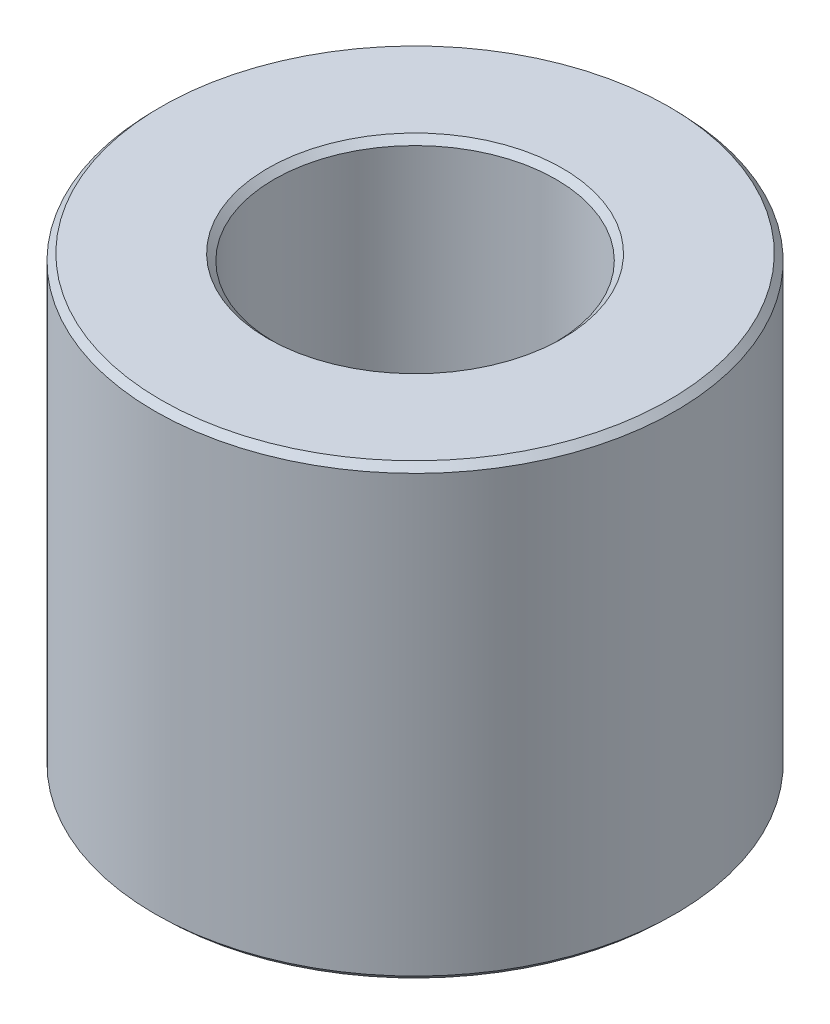
SolidWorks part; units mm, degrees
ref_plane "Front Plane" through (0, 0, 0) normal (0, 0, 1) x (1, 0, 0)
ref_plane "Top Plane" through (0, 0, 0) normal (0, 1, 0) x (1, 0, 0)
ref_plane "Right Plane" through (0, 0, 0) normal (1, 0, 0) x (0, 0, -1)
sketch "Sketch1" plane through (0, 0, 0) normal (0, 1, 0) x (1, 0, 0)
  circle A0 centre (0, 0) radius 45
  dimension "SLEEVE_OD" = 90
extrude "Boss-Extrude1" add sketch "Sketch1" along normal blind 77.4789
sketch "Sketch2" plane through (0, 0, 0) normal (0, 1, 0) x (1, 0, 0)
  circle A0 centre (0, 0) radius 24.3603
  dimension "BORE_D" = 48.7206
extrude "Cut-Extrude1" cut sketch "Sketch2" along normal through all
chamfer "Chamfer1" distance 1.127 angle 43.864 4 edges at (0, 77.4789, 24.3603) (0, 0, 24.3603) (0, 0, 45) (0, 77.4789, 45) first distance on face at (0, 77.4789, 24.3603) first distance on face at (0, 0, 24.3603) first distance on face at (0, 77.4789, 45)
